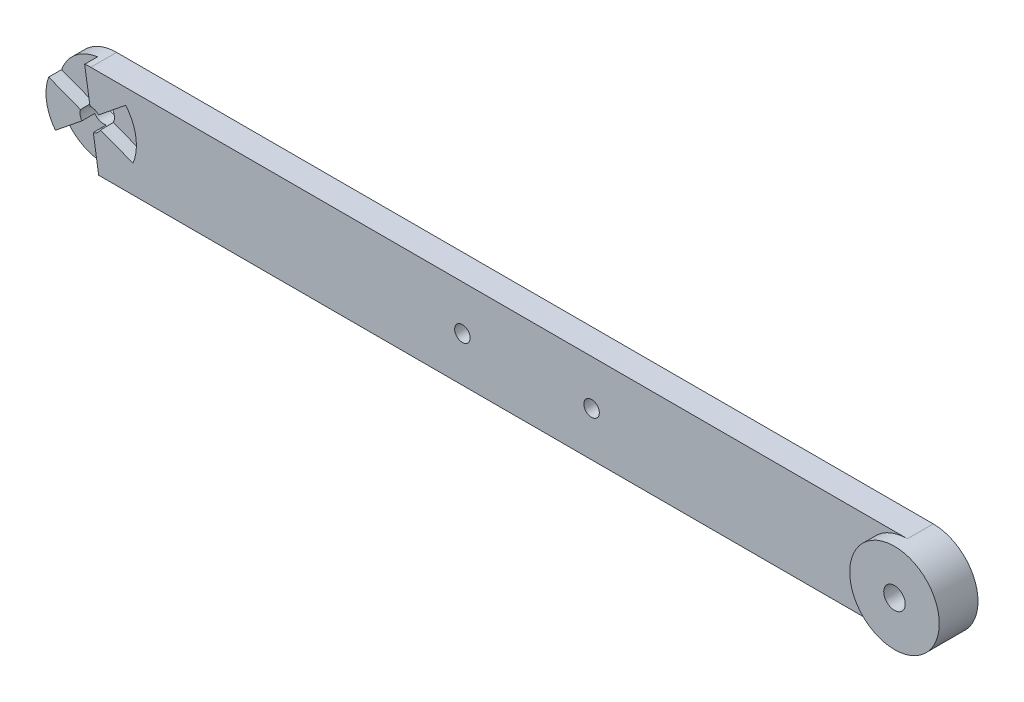
SolidWorks part; units mm, degrees
ref_plane "Front Plane" through (0, 0, 0) normal (0, 0, 1) x (1, 0, 0)
ref_plane "Top Plane" through (0, 0, 0) normal (0, 1, 0) x (1, 0, 0)
ref_plane "Right Plane" through (0, 0, 0) normal (1, 0, 0) x (0, 0, -1)
sketch "Sketch1" plane through (0, 0, 0) normal (0, 0, 1) x (1, 0, 0)
  line L0 (189.7, -10.4) -> (0, -10.4)
  line L1 (189.7, 10.4) -> (0, 10.4)
  circle A4 centre (0, 0) radius 2.5
  circle A5 centre (189.7, 0) radius 2.5
  arc A6 (0, 10.4) -> (0, -10.4) centre (0, 0) ccw
  arc A7 (189.7, -10.4) -> (189.7, 10.4) centre (189.7, 0) ccw
  arc A9 (0, -10.4) -> (0, 10.4) centre (0, 0) ccw construction
  circle A10 centre (0, 0) radius 10.4 construction
  arc A11 (189.7, 10.4) -> (189.7, -10.4) centre (189.7, 0) ccw construction
  circle A12 centre (189.7, 0) radius 10.4 construction
  circle A13 centre (189.7, 0) radius 1.4996 construction
  circle A15 centre (0, 0) radius 2.4001
  point P11 (170.2346, 97.4995)
  point P18 (75.4, 97.5)
  dimension "D1" = 5
  dimension "D3" = 1.0004
  dimension "D4" = 4.8001
  dimension "D2" = 10.4
  dimension "D5" = 189.7
extrude "Boss-Extrude1" add sketch "Sketch1" along normal blind 6 contours L0 A7 L1 A6 A4 A5 region at (94.85, 0, 0)
sketch "Sketch6" plane through (0, 0, 0) normal (0, 0, -1) x (-1, 0, 0)
  line L0 (0, 0) -> (6.6622, 8.2447) construction
  line L1 (0, 0) -> (-10.4, 0) construction
  line L2 (0, 0) -> (9.892, 3.8091) construction
  line L3 (0, 0) -> (1.6472, 10.4712) construction
  line L4 (2.3974, 0.7088) -> (9.9638, 3.6224)
  line L5 (0.1897, 2.4928) -> (1.4497, 10.5023)
  line L6 (-0.5848, -2.4306) -> (-1.8448, -10.4401)
  line L7 (0.0719, -0.1866) -> (9.9638, 3.6224) construction
  line L8 (-0.1976, 0.0311) -> (1.4497, 10.5023) construction
  line L9 (2.064, -1.4107) -> (8.3704, -6.5066)
  line L10 (0.1257, 0.1556) -> (8.3704, -6.5066) [skipped]
  line L11 (-0.1976, 0.0311) -> (-1.8448, -10.4401) [skipped]
  line L12 (0.0719, -0.1866) -> (-9.8201, -3.9957) [skipped]
  line L13 (0.1257, 0.1556) -> (-8.119, 6.8177) [skipped]
  line L14 (-1.8126, 1.7218) -> (-8.119, 6.8177)
  line L15 (-2.2537, -1.0821) -> (-9.8201, -3.9957)
  circle A0 centre (0, 0) radius 10.4 construction
  arc A1 (0, -10.4) -> (0, 10.4) centre (0, 0) ccw construction
  arc A2 (9.9621, 3.6217) -> (1.4494, 10.5004) centre (0, 0) ccw
  arc A3 (9.9621, 3.6217) -> (1.4494, 10.5004) centre (0, 0) ccw
  arc A4 (9.9621, 3.6217) -> (1.4494, 10.5004) centre (0, 0) ccw
  circle A5 centre (0, 0) radius 2.5 construction
  arc A6 (2.3974, 0.7088) -> (0.1897, 2.4928) centre (0, 0) ccw
  arc A7 (-0.5848, -2.4306) -> (2.064, -1.4107) centre (0, 0) ccw
  circle A8 centre (0, 0) radius 10.6 construction
  arc A9 (-1.8445, -10.4383) -> (8.369, -6.5054) centre (0, 0) ccw
  arc A10 (-1.8126, 1.7218) -> (-2.2537, -1.0821) centre (0, 0) ccw
  arc A11 (-8.1176, 6.8165) -> (-9.8183, -3.995) centre (0, 0) ccw
  point P8 (-0.7033, -1.0005)
  point P13 (7.6704, -5.9409)
  point P14 (0.0719, -0.1866)
  point P15 (9.124, 3.299)
  point P22 (10.1368, 3.0991)
  point P27 (0, 0)
  point P34 (0, 0)
  point P51 (0, 0)
  dimension "D3" = 60
  dimension "D2" = 128.94
  dimension "D4" = 30
  dimension "D6" = 0.2
  dimension "D8" = 3
  dimension "D1" = 0.2
  dimension "D5" = 0.2
  dimension "D7" = 3
extrude "Cut-Extrude3" cut sketch "Sketch6" against normal blind 3 contours L5 L4 | L9 L6 | L14 A11 L15 region at (-4.3826, 5.4237, 0) region at (-2.5057, -6.5073, 0) region at (6.8883, 1.0836, 0)
sketch "Sketch4" plane through (0, 0, 0) normal (0, 0, -1) x (-1, 0, 0)
  arc A0 (-189.7, 10.4) -> (-189.7, -10.4) centre (-189.7, 0) ccw construction
  arc A1 (-189.7, 10.4) -> (-189.7, -10.4) centre (-189.7, 0) ccw
  arc A2 (-189.7, 10.4) -> (-189.7, -10.4) centre (-189.7, 0) cw
  circle A3 centre (-189.7, 0) radius 2.5 construction
  circle A4 centre (-189.7, 0) radius 2.5
extrude "Boss-Extrude2" add sketch "Sketch4" along normal blind 3
mirror "Mirror1" about plane through (0, 0, 0) normal (0, 0, 1) of bodies 103
sketch "Sketch7" plane through (0, 0, -6) normal (0, 0, -1) x (-1, 0, 0)
  point P0 (-116.3361, -0.0508)
  point P3 (-86.3362, 0.0015)
delete or keep bodies "Body-Delete/Keep 1" type delete bodies bodies 103
hole_wizard "M3 Clearance Hole1" positions "Sketch7" profile "Sketch8" hole size "M3" standard "ANSI Metric" end condition through all
sketch "Sketch8" plane through (116.3361, -0.0508, -6) normal (1, 0, 0) x (0, 1, 0)
  line L0 (0, 0) -> (0, 9)
  line L1 (0, 9) -> (1.8, 9)
  line L2 (1.8, 9) -> (1.8, 0)
  line L5 (1.8, 0) -> (0, 0)
  line L11 (0, -6.35) -> (0, 107.95) construction
  dimension "Thru Hole Dia." = 3.6
  dimension "Thru Hole Depth" = 9
